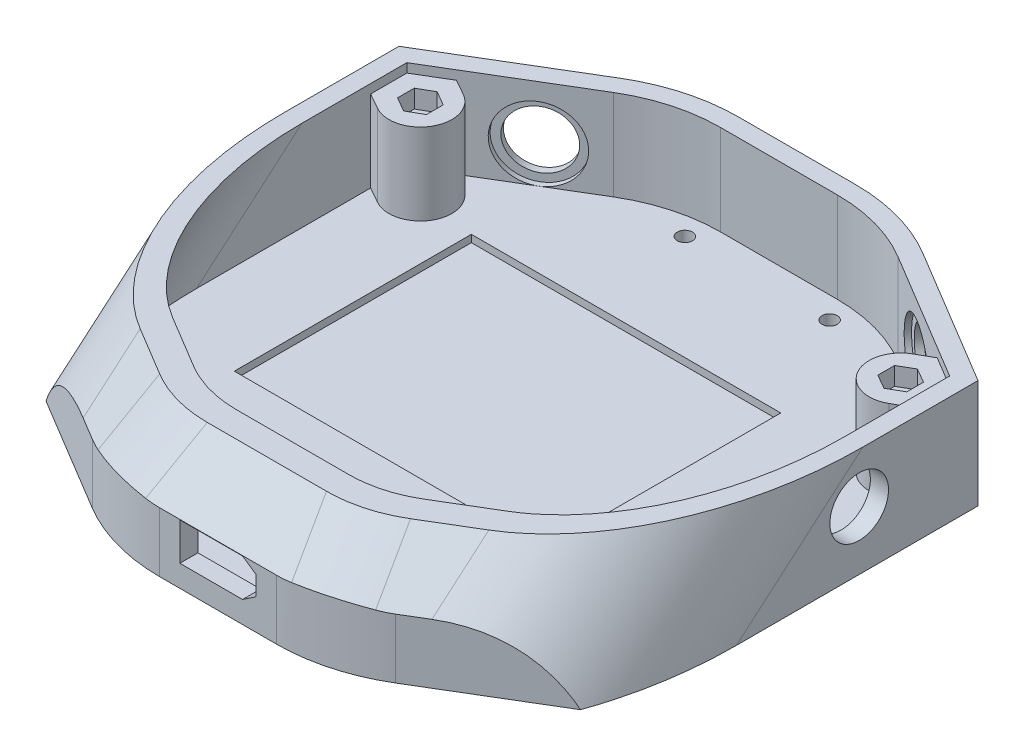
SolidWorks part; units mm, degrees
ref_plane "Front Plane" through (0, 0, 0) normal (0, 0, 1) x (1, 0, 0)
ref_plane "Top Plane" through (0, 0, 0) normal (0, 1, 0) x (1, 0, 0)
ref_plane "Right Plane" through (0, 0, 0) normal (1, 0, 0) x (0, 0, -1)
sketch "Sketch3" plane through (0, 0, 0) normal (0, 1, 0) x (1, 0, 0)
  line L0 (-80, 0) -> (80, 0) construction
  line L1 (80, 0) -> (80, -100)
  line L2 (80, -100) -> (30, -130)
  line L3 (30, -130) -> (-30, -130)
  line L4 (0, -130) -> (0, 0) construction
  line L5 (-80, -100) -> (-30, -130)
  line L6 (-80, 0) -> (-80, -100)
  line L7 (-80, 0) -> (-30, 30)
  line L8 (-30, 30) -> (30, 30)
  line L9 (30, 30) -> (80, 0)
  point P10 (0, 0)
  point P13 (0, 30)
  dimension "D1" = 80
  dimension "D2" = 100
  dimension "D3" = 30
  dimension "D4" = 30
  dimension "D5" = 30
extrude "Boss-Extrude1" add sketch "Sketch3" along normal blind 30
chamfer "Chamfer1" distance 13.5 angle 45 3 edges at (55, 30, 115) (0, 30, 130) (-55, 30, 115)
fillet "Fillet1" radius 50 6 edges at (30, 8.25, 130) (-80, 23.25, 92.1282) (80, 23.25, 92.1282) (28.1304, 23.25, 123.25) (-28.1304, 23.25, 123.25) (-30, 8.25, 130)
fillet "Fillet2" radius 50 2 edges at (-30, 15, -30) (30, 15, -30)
shell "Shell1" thickness 5 removed face at (0, 30, 45.3245)
sketch "Sketch4" plane through (0, 0, 130) normal (0, 0, 1) x (1, 0, 0)
  line L0 (16.1508, 16.5) -> (-16.1508, 16.5) construction
  line L1 (-10.3, 16.15) -> (6.7, 16.15) construction
  line L2 (6.7, 16.15) -> (10.3, 13.7) construction
  line L3 (10.3, 13.7) -> (10.3, 8.7) construction
  line L4 (10.3, 8.7) -> (6.7, 6.25) construction
  line L5 (6.7, 6.25) -> (-10.3, 6.25) construction
  line L6 (-10.3, 6.25) -> (-10.3, 16.15) construction
  line L7 (10.3, 11.2) -> (-10.3, 11.2) construction
  line L8 (10.55, 13.8323) -> (10.55, 8.5677)
  line L9 (10.55, 8.5677) -> (6.777, 6)
  line L10 (6.777, 6) -> (-10.55, 6)
  line L11 (-10.55, 6) -> (-10.55, 16.4)
  line L12 (-10.55, 16.4) -> (6.777, 16.4)
  line L13 (6.777, 16.4) -> (10.55, 13.8323)
  line L15 (-16.1508, 5) -> (16.1508, 5) construction
  point P14 (0, 11.2)
  point P15 (0, 16.5)
  dimension "D1" = 17
  dimension "D2" = 9.9
  dimension "D3" = 5
  dimension "D4" = 3.6
  dimension "D6" = 1
  dimension "D5" = 0.25
extrude "Cut-Extrude1" cut sketch "Sketch4" against normal up to next
sketch "Sketch5" plane through (0, 5, 0) normal (0, 1, 0) x (1, 0, 0)
  line L1 (-50, -10) -> (35.5, -10)
  line L2 (-50, -10) -> (-50, -75.5)
  line L3 (-50, -75.5) -> (35.5, -75.5)
  line L4 (35.5, -10) -> (35.5, -75.5)
  dimension "D1" = 85.5
  dimension "D2" = 65.5
  dimension "D3" = 50
  dimension "D4" = 10
extrude "Cut-Extrude2" cut sketch "Sketch5" against normal blind 2
sketch "Sketch6" plane through (21.1765, 0, -35.2941) normal (0.5145, 0, -0.8575) x (-0.8575, 0, -0.5145)
  line L2 (-39.2594, 15.1203) -> (-39.2594, 0) construction
  line L3 (-24.1391, 15.1203) -> (-39.2594, 15.1203) construction
  line L5 (-68.5994, 0) -> (-24.1391, 0) construction
  line L6 (-24.1391, 0) -> (-24.1391, 30) construction
  line L7 (-65.7685, 5) -> (-24.1391, 5) construction
  circle A0 centre (-39.2594, 15.1203) radius 10.1203
  dimension "D1" = 20.2406
extrude "Cut-Extrude3" cut sketch "Sketch6" against normal blind 1.488
sketch "Sketch7" plane through (18.604, 0, -31.0067) normal (-0.5145, 0, 0.8575) x (0.8575, 0, 0.5145)
  circle A1 centre (39.2594, 15.1203) radius 10.1203
  circle A2 centre (39.2594, 15.1203) radius 10.1203
  dimension "D2" = 0
extrude "Cut-Extrude4" cut sketch "Sketch7" against normal blind 1.488
sketch "Sketch8" plane through (21.1765, 0, -35.2941) normal (0.5145, 0, -0.8575) x (-0.8575, 0, -0.5145)
  circle A0 centre (-39.2594, 15.1203) radius 7.9375
  dimension "D1" = 15.875
extrude "Cut-Extrude5" cut sketch "Sketch8" against normal up to next
mirror "Mirror1" about plane through (0, 0, 0) normal (1, 0, 0) of "Cut-Extrude3", "Cut-Extrude4", "Cut-Extrude5"
sketch "Sketch9" plane through (0, 30, 0) normal (0, 1, 0) x (1, 0, 0)
  line L2 (-75, -2.831) -> (-66.4251, 2.314)
  line L3 (-39.3031, 18.5872) -> (-75, -2.831) construction
  line L4 (-75, -2.831) -> (-75, -60.9491) construction
  line L5 (-75, -2.831) -> (-75, -12.831)
  line L6 (-66.4251, 2.314) -> (-62.0741, -0.1495)
  line L7 (-70.649, -15.2944) -> (-75, -12.831)
  arc A1 (-62.0741, -0.1495) -> (-70.649, -15.2944) centre (-66.3615, -7.722) cw
  dimension "D1" = 10
  dimension "D2" = 10
  dimension "D3" = 5
extrude "Boss-Extrude2" add sketch "Sketch9" along normal offset from surface (22.5 mm away) 2.5 from surface at -25 up to face at (0, 30, 43.9845) starting at face at (0, 5, 44.5926)
sketch "Sketch10" plane through (0, 30, 0) normal (0, 1, 0) x (1, 0, 0)
  line L1 (-70.3615, -5.4126) -> (-70.3615, -10.0314)
  line L2 (-70.3615, -10.0314) -> (-66.3615, -12.3408)
  line L3 (-66.3615, -12.3408) -> (-62.3615, -10.0314)
  line L4 (-62.3615, -10.0314) -> (-62.3615, -5.4126)
  line L5 (-62.3615, -5.4126) -> (-66.3615, -3.1032)
  line L6 (-66.3615, -3.1032) -> (-70.3615, -5.4126)
  circle A0 centre (-66.3615, -7.722) radius 4 construction
  arc A2 (-70.649, -15.2944) -> (-62.0741, -0.1495) centre (-66.3615, -7.722) ccw construction
  dimension "D1" = 8
extrude "Cut-Extrude6" cut sketch "Sketch10" against normal blind 5 from surface at -2.5 contours L5 L6 L1 L2 L3 L4 starting at face at (-68.3151, 27.5, 6.6159)
mirror "Mirror2" about plane through (0, 0, 0) normal (1, 0, 0) of "Boss-Extrude2", "Cut-Extrude6"
sketch "Sketch11" plane through (0, 5, 0) normal (0, 1, 0) x (1, 0, 0)
  line L0 (16.1508, 25) -> (-16.1508, 25) construction
  line L1 (-50, -75.5) -> (35.5, -75.5) construction
  line L2 (-50, -75.5) -> (35.5, -75.5) construction
  line L3 (-7.25, -75.5) -> (-27.25, -75.5) construction
  line L4 (0, -16.5) -> (0, 16.5) construction
  circle A1 centre (-27.25, -95.5) radius 2.1
  circle A4 centre (-27.25, -95.5) radius 5 construction
  circle A5 centre (-20, 19) radius 2.1
  dimension "D1" = 20
  dimension "D2" = 4.2
  dimension "D5" = 10
  dimension "D8" = 4.2
  dimension "D6" = 20
  dimension "D7" = 20
  dimension "D9" = 6
extrude "Cut-Extrude7" cut sketch "Sketch11" against normal through all
mirror "Mirror3" about plane through (0, 0, 0) normal (1, 0, 0) of "Cut-Extrude7"
sketch "Sketch12" plane through (80, 0, 0) normal (1, 0, 0) x (0, 0, -1)
  line L1 (-12.831, 27.5) -> (-12.831, 5) construction
  circle A0 centre (-32.831, 16.25) radius 8.1
  point P10 (-12.831, 16.25)
  dimension "D1" = 16.2
  dimension "D2" = 20
extrude "Cut-Extrude8" cut sketch "Sketch12" against normal up to next
